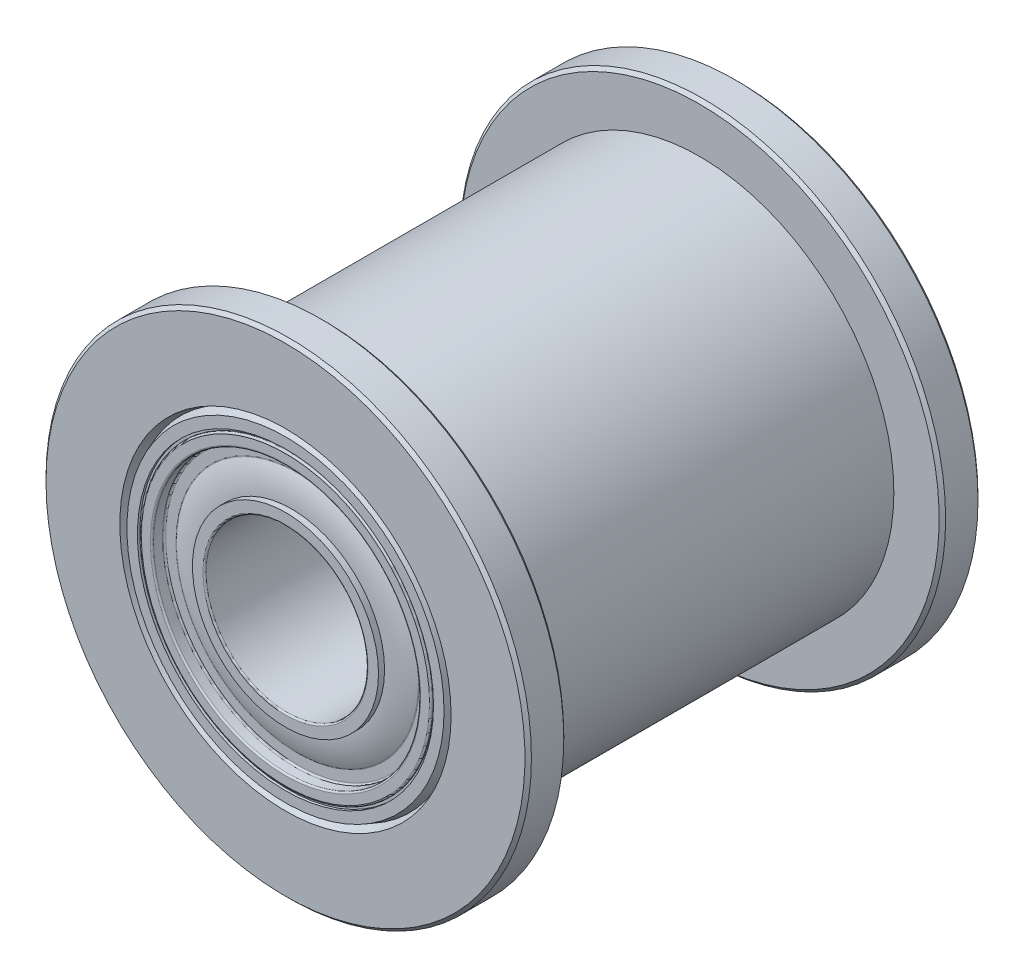
SolidWorks part; units mm, degrees
ref_plane "Front" through (0, 0, 0) normal (0, 0, 1) x (1, 0, 0)
ref_plane "Top" through (0, 0, 0) normal (0, 1, 0) x (1, 0, 0)
ref_plane "Right" through (0, 0, 0) normal (1, 0, 0) x (0, 0, -1)
sketch "Sketch1" plane through (0, 0, 0) normal (1, 0, 0) x (0, 0, -1)
  line L0 (-7, 0) -> (7, 0) construction
  line L1 (7, 7.5) -> (7, -7.5) construction
  line L2 (7, 7.5) -> (5.8, 7.5) construction
  line L3 (7, 2.5) -> (7, -2.5) construction
  line L4 (7, 6) -> (7, -6) construction
  line L5 (4.5, 0) -> (-4.5, 0) construction
  line L6 (5.8, 7.5) -> (5.8, 6) construction
  dimension "D3" = 1.2
  dimension "Width" = 14
  dimension "OD" = 15
  dimension "ID" = 5
  dimension "Diameter" = 12
  dimension "Max Belt Width" = 9
  dimension "Groove Depth" = 1.5
sketch "Sketch2" plane through (0, 0, 0) normal (1, 0, 0) x (0, 0, -1)
  line L0 (7, 2.5) -> (0, 2.5)
  line L1 (7, 2.5) -> (7, 2.875)
  line L2 (7, 7.5) -> (7, -7.5) construction
  line L3 (7, 2.875) -> (6.625, 2.875) construction
  line L4 (6.8125, 4.125) -> (6.8125, 2.875) construction
  line L5 (7, 4.5) -> (0, 4.5)
  line L6 (6.625, 3.75) -> (6.625, 4.125)
  line L7 (7, 4.5) -> (7, 4.125)
  line L8 (7, 4.125) -> (6.625, 4.125)
  line L9 (6.625, 4.125) -> (6.625, 2.875) construction
  line L10 (0, 4.5) -> (0, 2.5)
  line L11 (6.8125, 2.875) -> (7, 2.875)
  arc A0 (6.625, 3.75) -> (6.8125, 2.875) centre (4.6771, 2.875) cw
  dimension "D1" = 1.5
  dimension "D2" = 0.375
revolve "Revolve1" add sketch "Sketch2" angle 360 about L0
mirror "Mirror1" about plane through (0, 0, 0) normal (0, 0, 1) of bodies 108
sketch "Sketch3" plane through (0, 0, 0) normal (1, 0, 0) x (0, 0, -1)
  line L0 (5.8, 7.5) -> (7, 7.5)
  line L1 (7, 7.5) -> (7, 5.1184)
  line L2 (7, 7.5) -> (7, -7.5) construction
  line L3 (7, 5.1184) -> (6.7, 5.0092)
  line L4 (6.7, 5.0092) -> (7, 4.9)
  line L5 (7, 4.9) -> (7, 4.575)
  line L6 (6.925, 4.5) -> (6.925, 4.575)
  line L7 (7, 4.5) -> (-7, 4.5) construction
  line L8 (6.925, 4.575) -> (7, 4.575)
  line L9 (5.8, 7.5) -> (5.8, 6)
  line L10 (5.8, 6) -> (-5.8, 6)
  line L11 (0, 6) -> (0, 4.5) construction
  line L12 (-6.925, 4.5) -> (6.925, 4.5)
  line L13 (-5.8, 7.5) -> (-5.8, 6)
  line L14 (-6.925, 4.575) -> (-7, 4.575)
  line L15 (-6.925, 4.5) -> (-6.925, 4.575)
  line L16 (-7, 4.9) -> (-7, 4.575)
  line L17 (-6.7, 5.0092) -> (-7, 4.9)
  line L18 (-7, 5.1184) -> (-6.7, 5.0092)
  line L19 (-7, 7.5) -> (-7, 5.1184)
  line L20 (-5.8, 7.5) -> (-7, 7.5)
  line L21 (6.7, 5.0092) -> (7, 5.0092) construction
  line L22 (6.85, 5.0092) -> (6.85, 4.5) construction
  dimension "D1" = 40
  dimension "D2" = 0.3
  dimension "D3" = 0.075
  dimension "D4" = 0.4
revolve "Revolve2" add sketch "Sketch3" angle 360 about L0
sketch "Sketch4" plane through (0, 0, 0) normal (0, 0, 1) x (1, 0, 0)
  line L0 (-0.6, 6) -> (0.6, 6)
  line L1 (-0.6, 6) -> (-0.6, 5.4) construction
  line L2 (-0.6, 5.4) -> (0.6, 5.4) construction
  line L3 (0.6, 5.4) -> (0.6, 6) construction
  line L4 (0, 6) -> (0, 5.4) construction
  arc A0 (0.6, 6) -> (-0.6, 6) centre (0, 6) cw
  dimension "D1" = 0.6
  dimension "D3" = 1.2
extrude "Cut-Extrude1" [suppressed] cut sketch "Sketch4" against normal up to surface and the other way up to surface up to face at (6, 0, -5.8) other way up to face at (7.5, 0, 5.8)
fillet "Fillet1" [suppressed] radius 0.05
pattern_circular "CirPattern3" [suppressed] count 20 over 360 of bodies 114
chamfer "Chamfer1" distance 0.1 angle 45 4 edges at (7.5, 0, -7) (7.5, 0, -5.8) (7.5, 0, 5.8) (7.5, 0, 7)
fillet "Fillet2" radius 0.05 10 edges at (3.75, 0, 6.625) (4.125, 0, 6.625) (4.5, 0, 7) (4.125, 0, 7) (2.5, 0, 7) (2.5, 0, -7) (4.5, 0, -7) (3.75, 0, -6.625) (4.125, 0, -7) (2.875, 0, -7)
combine bodies "Combine1" operation type add bodies to combine 110 109
ref_axis "Center Axis 1" through (0, 0, -6.95) along (0, 0, 1)
ref_plane "Contact Plane 1" through (0, 0, -4.5) normal (0, 0, 1) x (1, 0, 0)
ref_plane "Contact Plane 2" through (0, 0, 4.5) normal (0, 0, 1) x (1, 0, 0)
equation "\"D1@Sketch4\"=\"Groove Depth@Sketch1\"/2.5"
equation "\"D3@Sketch4\"=\"Diameter@Sketch1\"/10"
equation "\"D2@Sketch3\"=\"D3@Sketch1\"/4"
equation "\"D1@Sketch2\"=(\"OD@Sketch1\"-\"Diameter@Sketch1\")/2"
equation "\"D2@Sketch2\"=\"D1@Sketch2\"/4"
equation "\"D3@Sketch3\"=\"D2@Sketch3\"/4"
equation "\"D4@Sketch3\"=\"D3@Sketch1\"/3"
